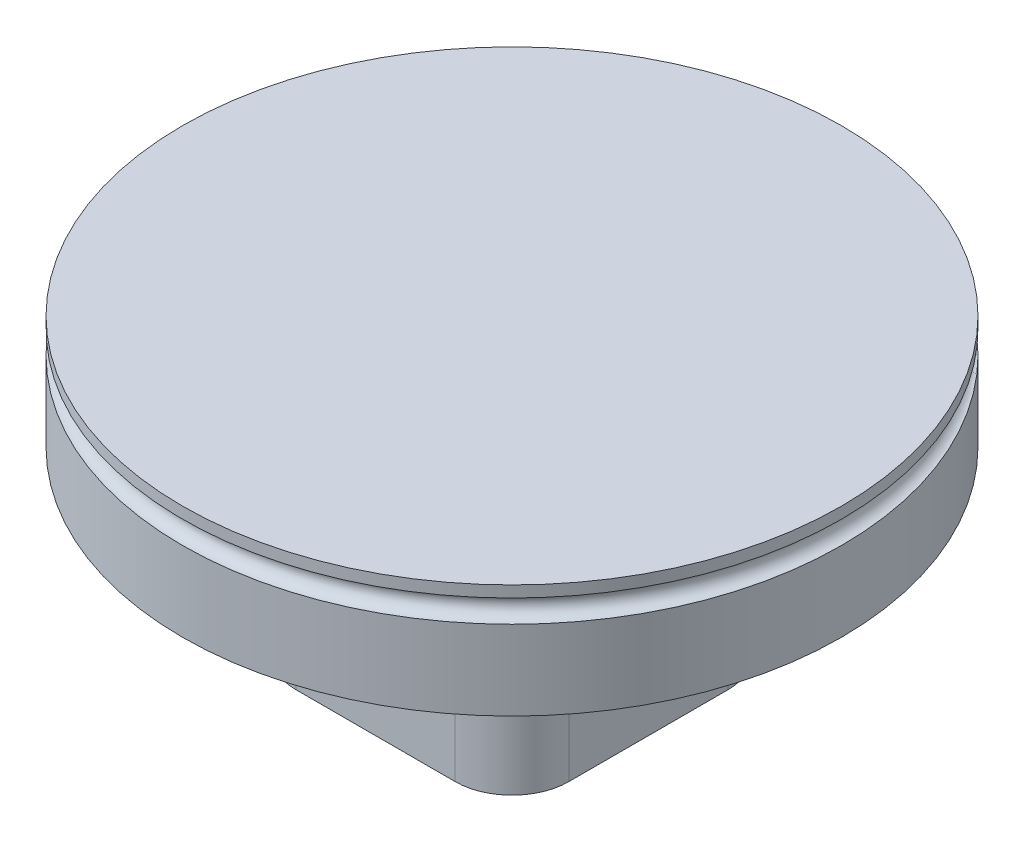
SolidWorks part; units mm, degrees
ref_plane "Front Plane" through (0, 0, 0) normal (0, 0, 1) x (1, 0, 0)
ref_plane "Top Plane" through (0, 0, 0) normal (0, 1, 0) x (1, 0, 0)
ref_plane "Right Plane" through (0, 0, 0) normal (1, 0, 0) x (0, 0, -1)
sketch "Sketch1" plane through (0, 0, 0) normal (0, 1, 0) x (1, 0, 0)
  circle A0 centre (0, 0) radius 29
  dimension "D1" = 58
extrude "Boss-Extrude1" add sketch "Sketch1" along normal blind 10
sketch "Sketch2" plane through (0, 0, 0) normal (0, -1, 0) x (1, 0, 0)
  line L5 (-10, -10) -> (10, 10) construction
  line L6 (-10, 10) -> (10, -10) construction
  line L7 (-12, -12) -> (12, -12)
  line L8 (-12, -12) -> (-12, 12)
  line L9 (-12, 12) -> (12, 12)
  line L10 (12, -12) -> (12, 12)
  line L11 (-12, -12) -> (12, 12) construction
  line L12 (-12, 12) -> (12, -12) construction
  circle A1 centre (0, 0) radius 10
  point P0 (0, 0)
  dimension "D1" = 20
  dimension "D2" = 24
extrude "Boss-Extrude2" add sketch "Sketch2" along normal blind 16
sketch "Sketch3" plane through (12, 0, 0) normal (1, 0, 0) x (0, 0, -1)
  line L0 (12, -16) -> (-12, -16) construction
  circle A0 centre (0, -8) radius 3
  dimension "D1" = 6
  dimension "D2" = 8
extrude "Cut-Extrude1" cut sketch "Sketch3" against normal through all
fillet "Fillet1" radius 5 4 edges at (-12, -8, -12) (12, -8, -12) (12, -8, 12) (-12, -8, 12)
fillet "Fillet2" radius 2 8 edges at (-10.5355, 0, 10.5355) (0, 0, 12) (10.5355, 0, 10.5355) (12, 0, 0) (10.5355, 0, -10.5355) (0, 0, -12) (-10.5355, 0, -10.5355) (-12, 0, 0)
sketch "Sketch4" plane through (0, 0, 0) normal (0, 0, 1) x (1, 0, 0)
  line L0 (-29, 10) -> (-29, 0) construction
  line L1 (0, 0) -> (0, 10) construction
  line L2 (29, 10) -> (-29, 10) construction
  circle A0 centre (-29, 8) radius 1
  dimension "D1" = 2
  dimension "D2" = 2
revolve "Cut-Revolve1" cut sketch "Sketch4" angle 360 about L1
